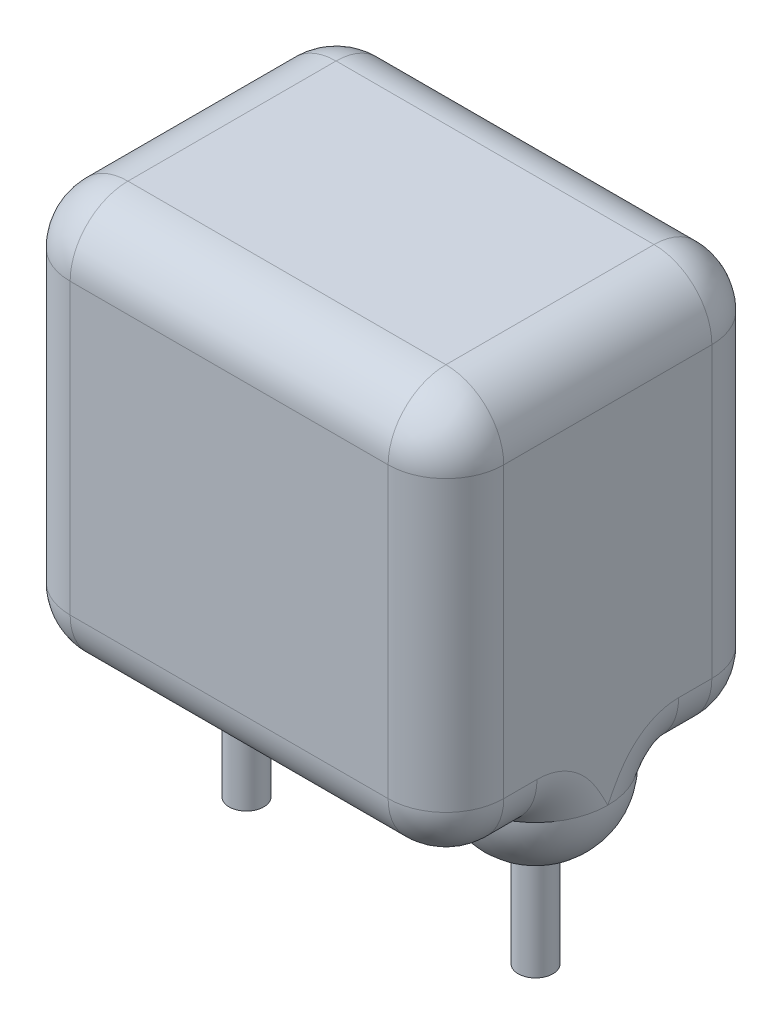
SolidWorks part; units mm, degrees
ref_plane "Спереди" through (0, 0, 0) normal (0, 0, 1) x (1, 0, 0)
ref_plane "Сверху" through (0, 0, 0) normal (0, 1, 0) x (1, 0, 0)
ref_plane "Справа" through (0, 0, 0) normal (1, 0, 0) x (0, 0, -1)
sketch "Эскиз1" plane through (0, 0, 0) normal (0, 1, 0) x (1, 0, 0)
  circle A0 centre (-2.5, 0) radius 0.3
  circle A1 centre (2.5, 0) radius 0.3
  point P4 (0, 0)
extrude "Бобышка-Вытянуть1" add sketch "Эскиз1" along normal blind 2 from offset 0.5 offset against normal yes
sketch "Эскиз3" plane through (0, 0, 0) normal (0, 0, 1) x (1, 0, 0)
  line L0 (-2.5, 1.5) -> (-2.5, 2.5) construction
  line L1 (-2.2, 1.5) -> (-2.8, 1.5) construction
  line L2 (-3.75, 1.5) -> (0, 1.5) construction
  line L3 (-3.75, 2.5) -> (-2.5, 2.5)
  line L4 (-2.5, 2.5) -> (-2.5, 1.25)
  arc A0 (-3.75, 2.5) -> (-2.5, 1.25) centre (-2.5, 2.5) ccw
  point P6 (0, 0)
  point P9 (0, 0)
revolve "Повернуть1" add sketch "Эскиз3" angle 360 about L4
sketch "Эскиз4" plane through (0, 0, 0) normal (0, 0, 1) x (1, 0, 0)
  line L0 (2.5, 1.5) -> (2.5, 2.5) construction
  line L1 (2.8, 1.5) -> (2.2, 1.5) construction
  line L2 (2.5, 2.5) -> (3.75, 2.5) construction
  line L3 (3.75, 2.5) -> (2.5, 2.5)
  line L4 (2.5, 2.5) -> (2.5, 1.25)
  arc A0 (3.75, 2.5) -> (2.5, 1.25) centre (2.5, 2.5) cw
revolve "Повернуть2" add sketch "Эскиз4" angle 360 about L4
sketch "Эскиз5" plane through (0, 2.5, 0) normal (0, 1, 0) x (1, 0, 0)
  line L1 (-3.75, 2.8) -> (3.75, 2.8)
  line L2 (-3.75, 2.8) -> (-3.75, -2.8)
  line L3 (-3.75, -2.8) -> (3.75, -2.8)
  line L4 (3.75, 2.8) -> (3.75, -2.8)
  point P4 (0, 0)
  point P5 (0, 0)
  point P6 (0, 0)
  point P7 (0, 0)
extrude "Бобышка-Вытянуть2" add sketch "Эскиз5" along normal blind 7
fillet "Скругление1" radius 1 14 edges at (-3.75, 2.5, 1.4) (-3.75, 2.5, -1.4) (-3.75, 6, -2.8) (0, 2.5, -2.8) (3.75, 6, -2.8) (3.75, 2.5, -1.4) (3.75, 2.5, 1.4) (-3.75, 6, 2.8) (3.75, 6, 2.8) (0, 2.5, 2.8) (0, 9.5, -2.8) (3.75, 9.5, 0) (0, 9.5, 2.8) (-3.75, 9.5, 0)
